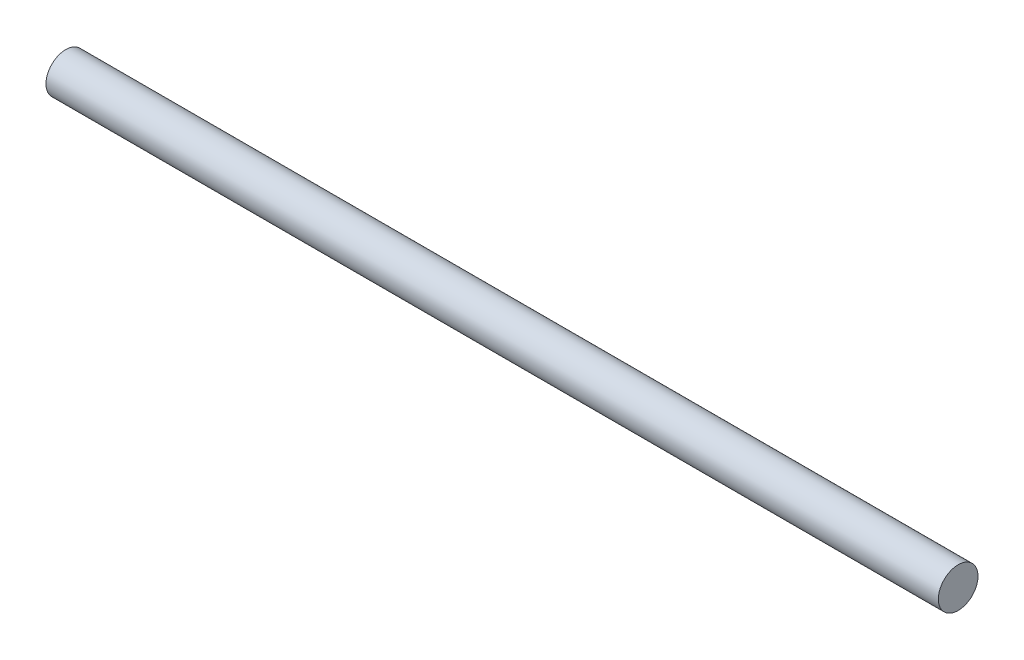
SolidWorks part; units mm, degrees
material "Chrome Stainless Steel"
ref_plane "Front Plane" through (0, 0, 0) normal (0, 0, 1) x (1, 0, 0)
ref_plane "Top Plane" through (0, 0, 0) normal (0, 1, 0) x (1, 0, 0)
ref_plane "Right Plane" through (0, 0, 0) normal (1, 0, 0) x (0, 0, -1)
other "Configuration Table"
sketch "Sketch1" plane through (0, 0, 0) normal (1, 0, 0) x (0, 0, -1)
  circle A0 centre (0, 0) radius 6
  dimension "D1" = 12
extrude "Boss-Extrude1" add sketch "Sketch1" along normal blind 270
ref_plane "Plane1" through (135, 0, 0) normal (1, 0, 0) x (0, 0, -1)
ref_axis "Axis1" through (270, 0, 0) along (-1, 0, 0)
